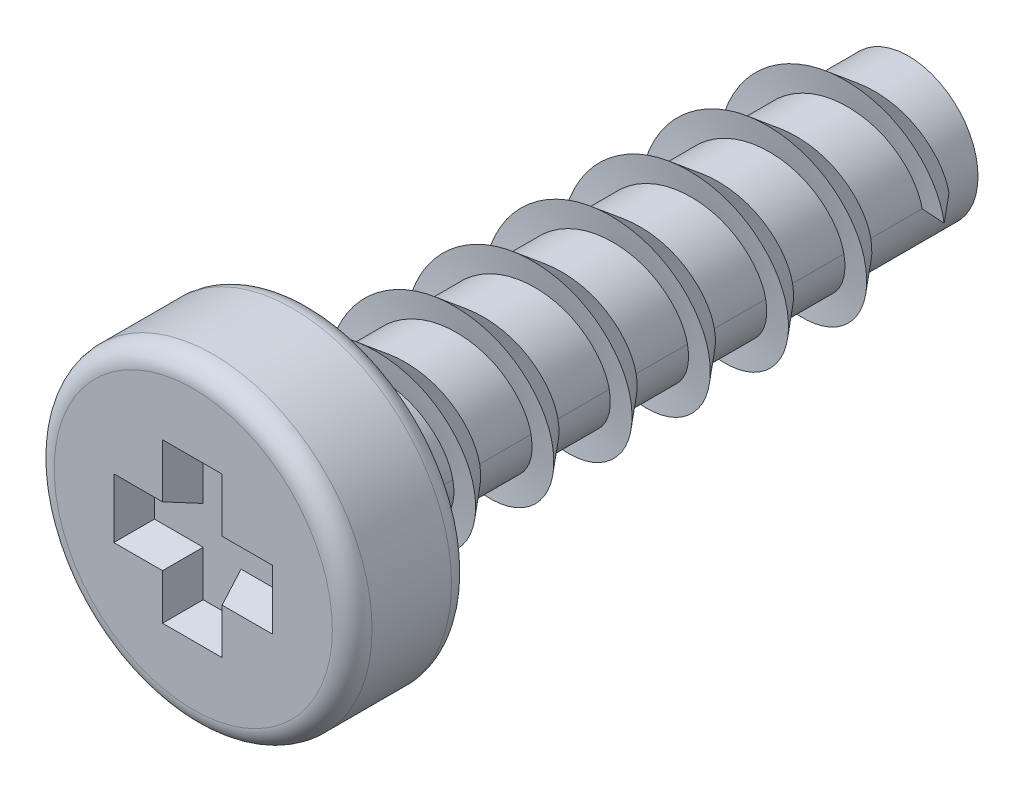
SolidWorks part; units mm, degrees
material "Cast Alloy Steel"
ref_plane "Front Plane" through (0, 0, 0) normal (0, 0, 1) x (1, 0, 0)
ref_plane "Top Plane" through (0, 0, 0) normal (0, 1, 0) x (1, 0, 0)
ref_plane "Right Plane" through (0, 0, 0) normal (1, 0, 0) x (0, 0, -1)
sketch "Sketch1" plane through (0, 0, 0) normal (0, 0, 1) x (1, 0, 0)
  circle A0 centre (0, 0) radius 0.889
extrude "Boss-Extrude1" add sketch "Sketch1" along normal blind 7.62
sketch "Sketch2" plane through (0, 0, 7.62) normal (0, 0, 1) x (1, 0, 0)
  circle A0 centre (0, 0) radius 2.032
extrude "Boss-Extrude2" add sketch "Sketch2" along normal blind 1.524
sketch "Sketch3" plane through (0, 0, 9.144) normal (0, 0, 1) x (1, 0, 0)
  line L0 (0, 2.079) -> (0, 1.016) construction
  line L1 (-2.1576, 0) -> (-1.016, 0) construction
  line L10 (-0.3931, -1.016) -> (0.3689, -1.016)
  line L11 (-0.0121, 0) -> (0, 0) construction
  line L12 (-0.3931, 0.3277) -> (-0.3931, 1.016)
  line L13 (-0.3931, 1.016) -> (0.3689, 1.016)
  line L14 (0.3689, 1.016) -> (0.3689, 0.3277)
  line L15 (0.3689, -0.4343) -> (0.3689, -1.016)
  line L16 (-0.3931, -0.4343) -> (-0.3931, -1.016)
  line L18 (-0.0121, 0) -> (0, 0) construction
  line L19 (-1.016, 0.3277) -> (-0.3931, 0.3277)
  line L20 (1.016, 0.3277) -> (1.016, -0.4343)
  line L21 (-1.016, 0.3277) -> (-1.016, -0.4343)
  line L22 (-1.016, -0.4343) -> (-0.3931, -0.4343)
  line L23 (0.3689, 0.3277) -> (1.016, 0.3277)
  line L24 (0.3689, -0.4343) -> (1.016, -0.4343)
  line L25 (0, 0) -> (0, -2.1523) construction
extrude "Cut-Extrude1" cut sketch "Sketch3" against normal blind 0.381 draft 20
ref_plane "Plane1" through (0, 0, 7.62) normal (0, 0, 1) x (1, 0, 0)
sketch "Sketch4" plane through (0, 0, 7.62) normal (0, 0, 1) x (1, 0, 0)
  circle A0 centre (0, 0) radius 0.889 construction
  circle A1 centre (0, 0) radius 0.889
curve "Helix/Spiral1" pitch 1 height 7 radius 0.889 centre (0, 0, 7.62) axis (0, 0, -1) start towards (1, 0, 0)
sketch "Sketch5" plane through (0, 0, 0) normal (0, 1, 0) x (1, 0, 0)
  line L0 (0.889, -0.3707) -> (1.1909, -0.7352)
  line L1 (0.889, -7.62) -> (0.889, 0) construction
  line L2 (1.1909, -0.7352) -> (0.7627, -0.7059)
  line L3 (0.7627, -0.7059) -> (0.889, -0.3707)
  spline S0 degree 3 poles (0.889, -7.62) (0.889, -7.5993) (0.8427, -7.5574) (0.645, -7.495) (0.3491, -7.4325) (0, -7.37) (-0.3491, -7.3075) (-0.645, -7.245) (-0.8427, -7.1825) (-0.9121, -7.12) (-0.8427, -7.0575) (-0.645, -6.995) (-0.2504, -6.9117) (0.2504, -6.8283) (0.645, -6.745) (0.8427, -6.6825) (0.9121, -6.62) (0.8427, -6.5575) (0.645, -6.495) (0.2504, -6.4117) (-0.2504, -6.3283) (-0.645, -6.245) (-0.8427, -6.1825) (-0.9121, -6.12) (-0.8427, -6.0575) (-0.645, -5.995) (-0.2504, -5.9117) (0.2504, -5.8283) (0.645, -5.745) (0.8427, -5.6825) (0.9121, -5.62) (0.8427, -5.5575) (0.645, -5.495) (0.2504, -5.4117) (-0.2504, -5.3283) (-0.645, -5.245) (-0.8427, -5.1825) (-0.9121, -5.12) (-0.8427, -5.0575) (-0.645, -4.995) (-0.2504, -4.9117) (0.2504, -4.8283) (0.645, -4.745) (0.8427, -4.6825) (0.9121, -4.62) (0.8427, -4.5575) (0.645, -4.495) (0.2504, -4.4117) (-0.2504, -4.3283) (-0.645, -4.245) (-0.8427, -4.1825) (-0.9121, -4.12) (-0.8427, -4.0575) (-0.645, -3.995) (-0.2504, -3.9117) (0.2504, -3.8283) (0.645, -3.745) (0.8427, -3.6825) (0.9121, -3.62) (0.8427, -3.5575) (0.645, -3.495) (0.2504, -3.4117) (-0.2504, -3.3283) (-0.645, -3.245) (-0.8427, -3.1825) (-0.9121, -3.12) (-0.8427, -3.0575) (-0.645, -2.995) (-0.2504, -2.9117) (0.2504, -2.8283) (0.645, -2.745) (0.8427, -2.6825) (0.9121, -2.62) (0.8427, -2.5575) (0.645, -2.495) (0.2504, -2.4117) (-0.2504, -2.3283) (-0.645, -2.245) (-0.8427, -2.1825) (-0.9121, -2.12) (-0.8427, -2.0575) (-0.645, -1.995) (-0.2504, -1.9117) (0.2504, -1.8283) (0.645, -1.745) (0.8427, -1.6825) (0.9121, -1.62) (0.8427, -1.5575) (0.645, -1.495) (0.2504, -1.4117) (-0.2504, -1.3283) (-0.645, -1.245) (-0.8427, -1.1825) (-0.9121, -1.12) (-0.8427, -1.0575) (-0.645, -0.995) (-0.3491, -0.9325) (0, -0.87) (0.3491, -0.8075) (0.645, -0.745) (0.8427, -0.6826) (0.889, -0.6407) (0.889, -0.62) knots 0 0 0 0 0.008929 0.017857 0.026786 0.035714 0.044643 0.053571 0.0625 0.071429 0.080357 0.089286 0.098214 0.116071 0.125 0.133929 0.142857 0.151786 0.160714 0.169643 0.1875 0.196429 0.205357 0.214286 0.223214 0.232143 0.241071 0.258929 0.267857 0.276786 0.285714 0.294643 0.303571 0.3125 0.330357 0.339286 0.348214 0.357143 0.366071 0.375 0.383929 0.401786 0.410714 0.419643 0.428571 0.4375 0.446429 0.455357 0.473214 0.482143 0.491071 0.5 0.508929 0.517857 0.526786 0.544643 0.553571 0.5625 0.571429 0.580357 0.589286 0.598214 0.616071 0.625 0.633929 0.642857 0.651786 0.660714 0.669643 0.6875 0.696429 0.705357 0.714286 0.723214 0.732143 0.741071 0.758929 0.767857 0.776786 0.785714 0.794643 0.803571 0.8125 0.830357 0.839286 0.848214 0.857143 0.866071 0.875 0.883929 0.901786 0.910714 0.919643 0.928571 0.9375 0.946429 0.955357 0.964286 0.973214 0.982143 0.991071 1 1 1 1 construction
sweep "Sweep1" add profiles "Sketch5" path "Helix/Spiral1"
fillet "Fillet1" radius 0.254 1 edges at (2.032, 0, 9.144)
fillet "Fillet2" radius 0.254 1 edges at (2.032, 0, 7.62)
